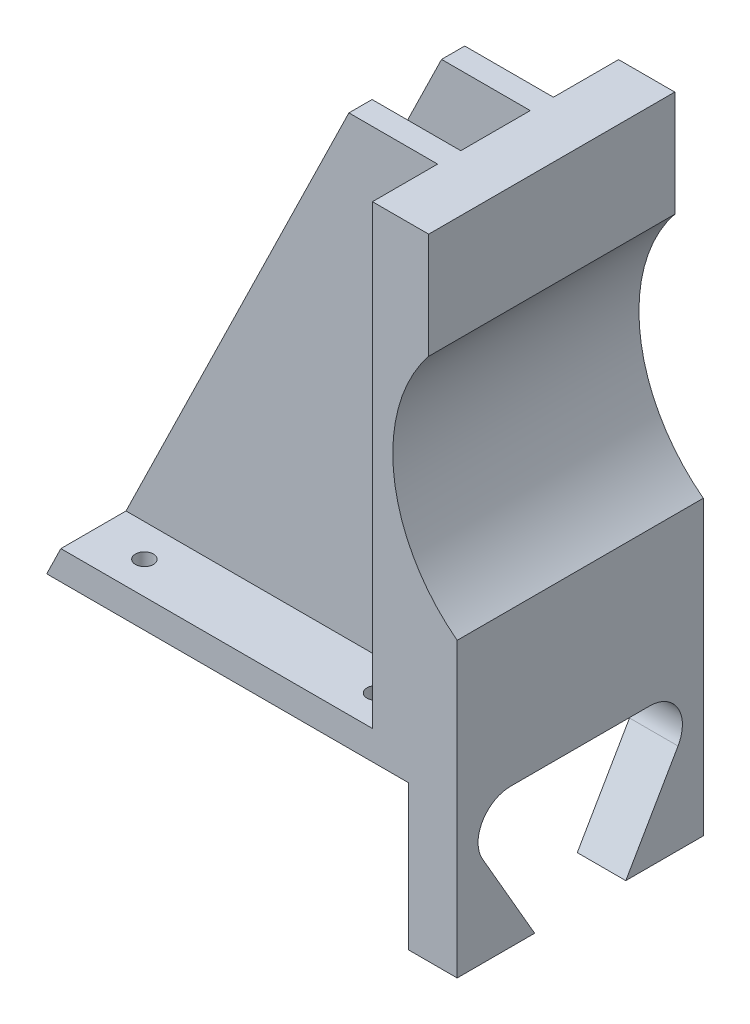
SolidWorks part; units mm, degrees
ref_plane "Front Plane" through (0, 0, 0) normal (0, 0, 1) x (1, 0, 0)
ref_plane "Top Plane" through (0, 0, 0) normal (0, 1, 0) x (1, 0, 0)
ref_plane "Right Plane" through (0, 0, 0) normal (1, 0, 0) x (0, 0, -1)
sketch "Sketch4" plane through (0, 0, 0) normal (0, 0, 1) x (1, 0, 0)
  line L0 (-25, -10) -> (31.7021, -10)
  line L1 (-25, -10) -> (25, -10) construction
  line L2 (-25, -10) -> (-25, 10) construction
  line L3 (-25, 10) -> (25, 10) construction
  line L4 (25, -10) -> (25, 10) construction
  line L5 (-25, -10) -> (25, 10) construction
  line L6 (-25, 10) -> (25, -10) construction
  line L7 (31.7021, -10) -> (31.7021, 30.3986)
  line L8 (27.7654, 62.4074) -> (27.7654, 77.0234)
  line L9 (27.7654, 77.0234) -> (7.7472, 77.0234)
  line L10 (7.7472, 77.0234) -> (-25, 10)
  line L11 (-25, 10) -> (-25, -10)
  arc A0 (27.7654, 62.4074) -> (31.7021, 30.3986) centre (45.316, 48.3194) ccw
  point P0 (0, 0)
  dimension "D1" = 50
  dimension "D2" = 20
extrude "Boss-Extrude2" add sketch "Sketch4" along normal blind 34
sketch "Sketch5" plane through (0, 0, 34) normal (0, 0, 1) x (1, 0, 0)
  line L0 (-23.0456, 14) -> (7.7472, 77.0234)
  line L1 (-25, -10) -> (25, -10)
  line L2 (-25, -10) -> (-25, 10)
  line L3 (-25, 10) -> (25, 10)
  line L4 (25, -10) -> (25, 10)
  line L5 (7.7472, 77.0234) -> (-25, 10) construction
  line L6 (7.7472, 77.0234) -> (20, 77.0234)
  line L7 (27.7654, 77.0234) -> (7.7472, 77.0234) construction
  line L8 (20, 77.0234) -> (20, 14)
  line L9 (20, 14) -> (-23.0456, 14)
  dimension "D1" = 50
  dimension "D2" = 20
  dimension "D3" = 4
  dimension "D4" = 45
extrude "Cut-Extrude1" cut sketch "Sketch5" against normal blind 9
sketch "Sketch6" plane through (0, 0, 0) normal (0, 0, -1) x (-1, 0, 0)
  line L0 (23.0456, 14) -> (-20, 14)
  line L1 (25, -10) -> (-25, -10)
  line L2 (25, -10) -> (25, 10)
  line L3 (25, 10) -> (-25, 10)
  line L4 (-25, -10) -> (-25, 10)
  line L5 (-7.7472, 77.0234) -> (25, 10) construction
  line L6 (-20, 14) -> (-20, 77.0234)
  line L7 (-27.7654, 77.0234) -> (-7.7472, 77.0234) construction
  line L8 (-20, 77.0234) -> (-7.7472, 77.0234)
  line L9 (-7.7472, 77.0234) -> (23.0456, 14)
  dimension "D1" = 50
  dimension "D2" = 20
  dimension "D3" = 45
  dimension "D4" = 4
extrude "Cut-Extrude2" cut sketch "Sketch6" against normal blind 9
sketch "Sketch7" plane through (0, 0, 9) normal (0, 0, -1) x (-1, 0, 0)
  line L1 (-25, 10) -> (27.0063, 10)
  line L2 (-25, 10) -> (-25, -11.6279)
  line L3 (-25, -11.6279) -> (27.0063, -11.6279)
  line L4 (27.0063, 10) -> (27.0063, -11.6279)
  dimension "D1" = 21.6279
  dimension "D2" = 52.0063
extrude "Cut-Extrude3" cut sketch "Sketch7" against normal through all
sketch "Sketch8" plane through (31.7021, 0, 0) normal (1, 0, 0) x (0, 0, -1)
  line L0 (-26.61, 8) -> (-7.38, 8)
  line L1 (-29.7004, 2.8571) -> (-19.979, -15.4295)
  line L2 (-14.011, -15.4295) -> (-4.2896, 2.8571)
  line L3 (-34, -10) -> (-34, 30.3986) construction
  line L5 (0, -10) -> (0, 30.3986) construction
  line L6 (-34, -10) -> (0, -10) construction
  line L7 (-34, -10) -> (-34, 10) construction
  line L8 (-34, 10) -> (0, 10) construction
  line L9 (0, -10) -> (0, 10) construction
  line L10 (-26.61, 4.5) -> (-7.38, 4.5) construction
  line L11 (-24.295, -13.8431) -> (-10.3108, -13.8431) construction
  arc A3 (-26.61, 8) -> (-29.7004, 2.8571) centre (-26.61, 4.5) ccw
  arc A4 (-7.38, 8) -> (-4.2896, 2.8571) centre (-7.38, 4.5) cw
  arc A5 (-14.011, -15.4295) -> (-19.979, -15.4295) centre (-16.995, -13.8431) cw
  dimension "D1" = 3.5
  dimension "D2" = 3.5
  dimension "D3" = 3.3794
  dimension "D4" = 19.23
  dimension "D5" = 20.71
  dimension "D6" = 20.71
  dimension "D7" = 7.39
  dimension "D8" = 2
  dimension "D9" = 20
sketch "Sketch9" plane through (31.7021, 0, 0) normal (1, 0, 0) x (0, 0, -1)
  line L0 (-26.615, 8.2493) -> (-7.385, 8.2493) construction
  line L1 (-4.3541, 2.999) -> (-13.9691, -13.651) construction
  line L2 (-29.6459, 2.999) -> (-20.0309, -13.651) construction
  line L4 (-34, 30.3986) -> (0, 30.3986) construction
  line L5 (-26.615, 4.7493) -> (-7.385, 4.7493) construction
  line L6 (-17, 4.7493) -> (-17, -11.9007) construction
  line L7 (-34, 10.1993) -> (0, 10.1993) construction
  line L8 (-34, -10) -> (-34, 30.3986) construction
  line L9 (0, -10) -> (0, 30.3986) construction
  line L10 (-26.615, 9.2493) -> (-7.385, 9.2493)
  line L11 (-3.4881, 2.4989) -> (-13.1031, -14.1511)
  line L12 (-30.5119, 2.4989) -> (-20.8969, -14.1511)
  arc A0 (-26.615, 8.2493) -> (-29.6459, 2.999) centre (-26.615, 4.7493) ccw construction
  arc A1 (-4.3541, 2.999) -> (-7.385, 8.2493) centre (-7.385, 4.7493) ccw construction
  arc A2 (-20.0309, -13.651) -> (-13.9691, -13.651) centre (-17, -11.9007) ccw construction
  arc A3 (-29.6459, 2.999) -> (-26.615, 8.2493) centre (-26.615, 4.7493) ccw construction
  arc A4 (-7.385, 8.2493) -> (-4.3541, 2.999) centre (-7.385, 4.7493) ccw construction
  arc A5 (-13.9691, -13.651) -> (-20.0309, -13.651) centre (-17, -11.9007) ccw construction
  arc A6 (-3.4881, 2.4989) -> (-7.385, 9.2493) centre (-7.385, 4.7493) ccw
  arc A7 (-20.8969, -14.1511) -> (-13.1031, -14.1511) centre (-17, -11.9007) ccw
  arc A8 (-26.615, 9.2493) -> (-30.5119, 2.4989) centre (-26.615, 4.7493) ccw
  point P21 (-17, 30.3986)
  dimension "D1" = 7
  dimension "D2" = 7
  dimension "D3" = 7
  dimension "D4" = 19.23
  dimension "D5" = 16.65
  dimension "D6" = 1.95
  dimension "D7" = 22.1
  dimension "D8" = 1
extrude "Cut-Extrude4" cut sketch "Sketch9" against normal through all
sketch "Sketch10" plane through (0, 10, 0) normal (0, -1, 0) x (1, 0, 0)
  line L0 (25, 23.2941) -> (25, 34) construction
  line L1 (25, 34) -> (-25, 34) construction
  line L3 (-25, 0) -> (25, 0) construction
  line L4 (-25, 34) -> (-25, 0) construction
  circle A0 centre (16, 29.5) radius 1.25
  circle A1 centre (16, 4.5) radius 1.25
  circle A2 centre (-16, 29.5) radius 1.25
  circle A3 centre (-16, 4.5) radius 1.25
  point P6 (16, 28.8163)
  point P17 (-16, 29.5)
  dimension "D3" = 2.5
  dimension "D4" = 2.5
  dimension "D6" = 4.5
  dimension "D7" = 4.5
  dimension "D8" = 4.5
  dimension "D10" = 2.5
  dimension "D11" = 2.5
  dimension "D1" = 25
  dimension "D2" = 9
  dimension "D5" = 4.5
  dimension "D9" = 9
  dimension "D12" = 9
extrude "Cut-Extrude5" cut sketch "Sketch10" against normal blind 10
sketch "Sketch11" plane through (20, 0, 0) normal (-1, 0, 0) x (0, 0, 1)
  line L0 (25, 77.0234) -> (9, 77.0234) construction
  line L1 (21.8, 40.7234) -> (12.2, 40.7234)
  line L2 (21.8, 40.7234) -> (21.8, 77.0234)
  line L3 (21.8, 77.0234) -> (12.2, 77.0234)
  line L4 (12.2, 40.7234) -> (12.2, 77.0234)
  line L5 (9, 14) -> (9, 77.0234) construction
  dimension "D1" = 9.6
  dimension "D2" = 3.2
  dimension "D3" = 36.3
extrude "Cut-Extrude6" cut sketch "Sketch11" along normal blind 24.6
sketch "Sketch12" plane through (0, 40.7234, 0) normal (0, 1, 0) x (1, 0, 0)
  line L0 (-4.6, -21.8) -> (20, -21.8) construction
  line L1 (-4.6, -12.2) -> (7.7, -12.2)
  line L2 (-4.6, -12.2) -> (-4.6, -21.8)
  line L3 (-4.6, -21.8) -> (7.7, -21.8)
  line L4 (7.7, -12.2) -> (7.7, -21.8)
extrude "Boss-Extrude3" add sketch "Sketch12" along normal blind 6
sketch "Sketch13" plane through (0, 0, 25) normal (0, 0, 1) x (1, 0, 0)
  line L0 (7.7, 40.7234) -> (20, 40.7234) construction
  line L1 (20, 14) -> (20, 77.0234) construction
  circle A0 centre (13.85, 43.7234) radius 1.5
  dimension "D2" = 3
  dimension "D1" = 3
  dimension "D3" = 6.15
extrude "Cut-Extrude7" cut sketch "Sketch13" against normal through all
equation "\"D1@Sketch9\"=3.5*2mm"
